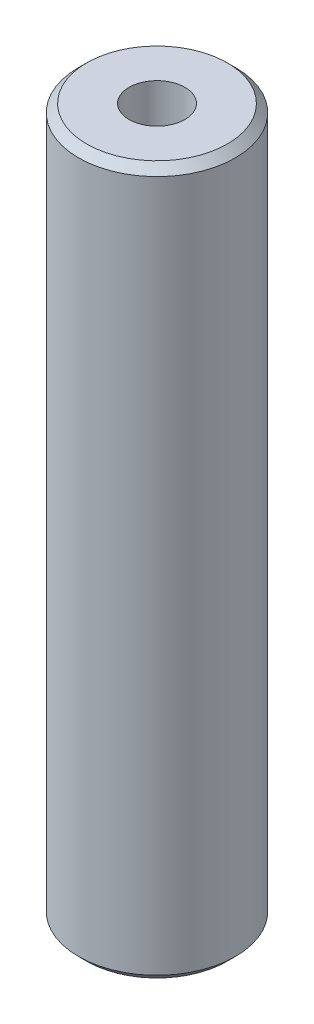
SolidWorks part; units mm, degrees
ref_plane "Front Plane" through (0, 0, 0) normal (0, 0, 1) x (1, 0, 0)
ref_plane "Top Plane" through (0, 0, 0) normal (0, 1, 0) x (1, 0, 0)
ref_plane "Right Plane" through (0, 0, 0) normal (1, 0, 0) x (0, 0, -1)
sketch "Sketch1" plane through (0, 0, 0) normal (0, 1, 0) x (1, 0, 0)
  circle A0 centre (0, 0) radius 27.5
  dimension "SHAFT_OD" = 55
extrude "Boss-Extrude1" add sketch "Sketch1" along normal blind 248.4152
sketch "Sketch2" plane through (0, 0, 0) normal (0, 1, 0) x (1, 0, 0)
  circle A0 centre (0, 0) radius 9.7965
  dimension "BORE_D" = 19.5931
extrude "Cut-Extrude1" cut sketch "Sketch2" along normal through all
chamfer "Chamfer1" distance 2.8158 angle 45 2 edges at (0, 248.4152, 27.5) (0, 0, 27.5)
